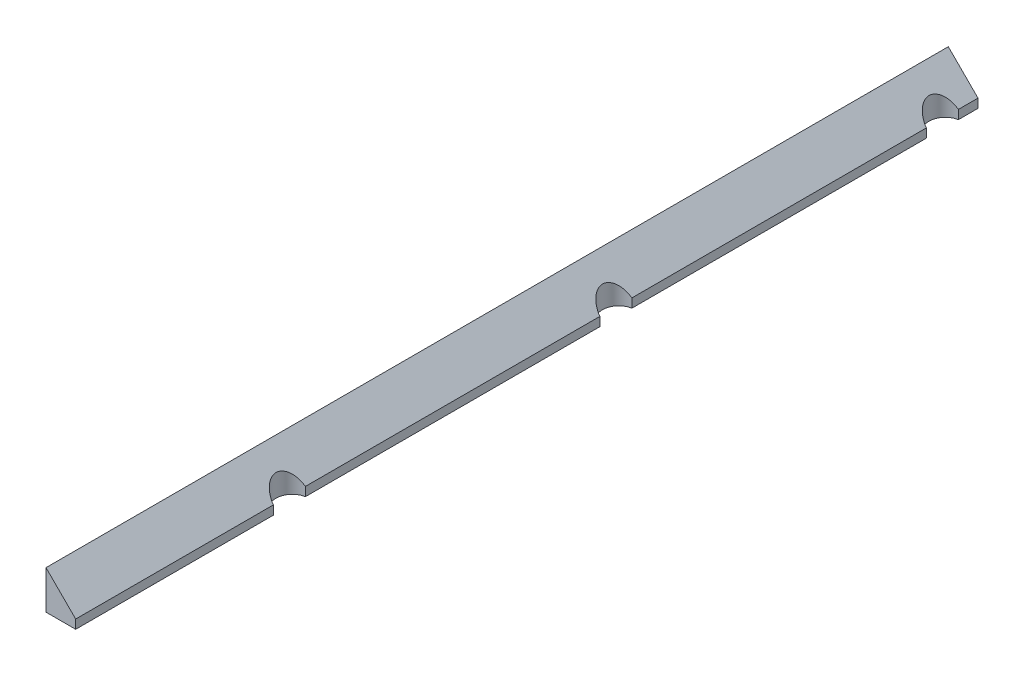
SolidWorks part; units mm, degrees
material "6061-T6 (SS)"
ref_plane "Front Plane" through (0, 0, 0) normal (0, 0, 1) x (1, 0, 0)
ref_plane "Top Plane" through (0, 0, 0) normal (0, 1, 0) x (1, 0, 0)
ref_plane "Right Plane" through (0, 0, 0) normal (1, 0, 0) x (0, 0, -1)
sketch "Sketch1" plane through (0, 0, 0) normal (0, 0, 1) x (1, 0, 0)
  line L5 (0, 0) -> (2.6, 0)
  line L6 (2.6, 0) -> (0, 2.6)
  line L7 (0, 2.6) -> (0, 0)
  line L11 (2, 0) -> (2, 0.6)
  dimension "D1" = 0.6
  dimension "D2" = 2.6
extrude "Boss-Extrude1" add sketch "Sketch1" against normal mid plane 72.8 contours L5 L11 L6 L7 region at (0.7917, 0.9042, 0)
sketch "Sketch2" plane through (0, 0, 0) normal (0, -1, 0) x (1, 0, 0)
  line L0 (2, -36.4) -> (2, 36.4) construction
  circle A12 centre (2.2, 0) radius 1.1
  circle A13 centre (2.2, 22) radius 1.1
  circle A14 centre (2.2, -22) radius 1.1
  dimension "D1" = 2.2
  dimension "D2" = 0.2
  dimension "D3" = 22
  dimension "D4" = 22
extrude "Cut-Extrude1" cut sketch "Sketch2" against normal up to surface (0.4 mm away) up to face at (1, 1.6, 0)
sketch "Sketch3" plane through (0, 0, 0) normal (0, -1, 0) x (1, 0, 0)
  line L1 (2, -20.9183) -> (2, -1.0817) construction
  circle A0 centre (2.2, 0) radius 1
  dimension "D1" = 2
  dimension "D2" = 0.2
extrude "Cut-Extrude2" [suppressed] cut sketch "Sketch3" against normal up to surface (0.4 mm away) up to face at (1.33, 1.27, 0)
sketch "Sketch4" plane through (0, 0, 0) normal (0, -1, 0) x (-1, 0, 0)
  line L0 (0, 36.4) -> (0, -36.4) construction
  line L1 (-2, 36.4) -> (0, 36.4)
  line L2 (-2, 36.4) -> (-2, 24.4)
  line L3 (-2, 24.4) -> (0, 24.4)
  line L4 (0, 36.4) -> (0, 24.4)
  dimension "D1" = 12
extrude "Cut-Extrude3" cut sketch "Sketch4" against normal up to vertex (2.6 mm away) up to point (0, 2.6, -36.4)
